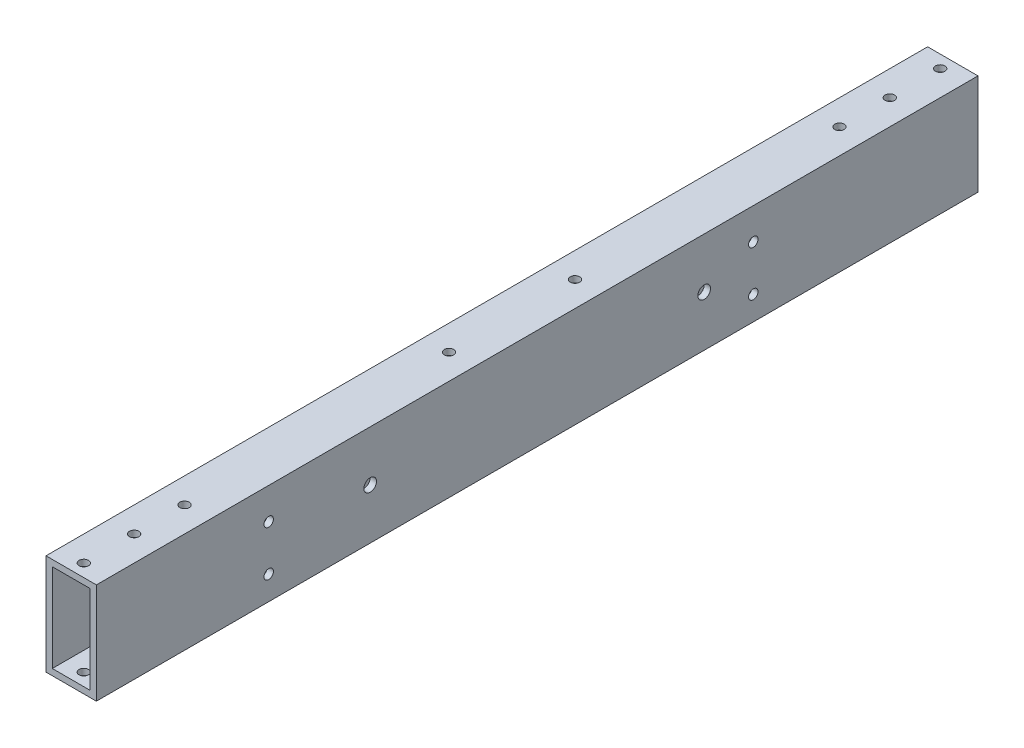
SolidWorks part; units mm, degrees
material "6063-T1"
ref_plane "Front Plane" through (0, 0, 0) normal (0, 0, 1) x (1, 0, 0)
ref_plane "Top Plane" through (0, 0, 0) normal (0, 1, 0) x (1, 0, 0)
ref_plane "Right Plane" through (0, 0, 0) normal (1, 0, 0) x (0, 0, -1)
sketch "Sketch1" plane through (0, 0, 0) normal (0, 0, 1) x (1, 0, 0)
  line L1 (-12.7, 25.4) -> (12.7, 25.4)
  line L2 (-12.7, 25.4) -> (-12.7, -25.4)
  line L3 (-12.7, -25.4) -> (12.7, -25.4)
  line L4 (12.7, 25.4) -> (12.7, -25.4)
  line L5 (-12.7, 25.4) -> (12.7, -25.4) construction
  line L6 (-12.7, -25.4) -> (12.7, 25.4) construction
  point P0 (0, 0)
  dimension "D1" = 25.4
  dimension "D2" = 50.8
extrude "Boss-Extrude1" add sketch "Sketch1" along normal blind 444.5
shell "Shell1" thickness 3.175 removed face at (0, 0, 0) removed face at (0, 0, 444.5)
sketch "Sketch2" plane through (0, 25.4, 0) normal (0, 1, 0) x (1, 0, 0)
  line L0 (12.7, 0) -> (-12.7, 0) construction
  line L1 (12.7, -222.25) -> (-14.2289, -222.25) construction
  line L2 (12.7, -444.5) -> (12.7, 0) construction
  circle A0 centre (0, -6.35) radius 2.3812
  circle A3 centre (0, -31.75) radius 2.3812
  circle A4 centre (0, -57.15) radius 2.3812
  circle A5 centre (0, -387.35) radius 2.3812
  circle A6 centre (0, -412.75) radius 2.3812
  circle A7 centre (0, -438.15) radius 2.3813
  dimension "D1" = 4.7625
  dimension "D2" = 6.35
  dimension "D3" = 3
extrude "Cut-Extrude1" cut sketch "Sketch2" against normal through all
sketch "Sketch3" plane through (-12.7, 0, 0) normal (-1, 0, 0) x (0, 0, 1)
  line L0 (222.25, 25.4) -> (222.25, -25.4) construction
  line L1 (444.5, 25.4) -> (0, 25.4) construction
  line L2 (444.5, -25.4) -> (0, -25.4) construction
  line L3 (0, 25.4) -> (0, -25.4) construction
  circle A0 centre (138.049, 0) radius 3.175
  circle A1 centre (306.451, 0) radius 3.175
  dimension "D1" = 6.35
  dimension "D2" = 138.049
  dimension "D3" = 25.4
extrude "Cut-Extrude2" cut sketch "Sketch3" against normal through all
sketch "Sketch4" plane through (0, 25.4, 0) normal (0, 1, 0) x (1, 0, 0)
  line L0 (12.7, -222.25) -> (-12.7, -222.25) construction
  line L1 (12.7, -444.5) -> (12.7, 0) construction
  line L2 (-12.7, -444.5) -> (-12.7, 0) construction
  line L3 (12.7, 0) -> (-12.7, 0) construction
  circle A0 centre (0, -190.5) radius 2.3812
  circle A1 centre (0, -254) radius 2.3813
  dimension "D1" = 4.7625
  dimension "D2" = 190.5
  dimension "D3" = 12.7
extrude "Cut-Extrude3" cut sketch "Sketch4" against normal through all
sketch "Sketch5" plane through (-12.7, 0, 0) normal (-1, 0, 0) x (0, 0, 1)
  line L1 (444.5, 25.4) -> (0, 25.4) construction
  line L2 (444.5, 25.4) -> (444.5, -25.4) construction
  line L3 (0, -25.4) -> (0, 25.4) construction
  circle A0 centre (357.632, 9.525) radius 2.3813
  circle A1 centre (357.632, -13.335) radius 2.3813
  circle A2 centre (113.284, 9.525) radius 2.3813
  circle A3 centre (113.284, -13.335) radius 2.3813
  point P14 (0, 0)
  point P15 (0, 0)
  point P16 (0, 0)
  dimension "D3" = 4.7625
  dimension "D4" = 4.7625
  dimension "D9" = 4.7625
  dimension "D10" = 4.7625
  dimension "D1" = 86.868
  dimension "D2" = 86.868
  dimension "D5" = 15.875
  dimension "D6" = 22.86
  dimension "D7" = 113.284
  dimension "D8" = 113.284
  dimension "D11" = 22.86
extrude "Cut-Extrude4" cut sketch "Sketch5" against normal through all
